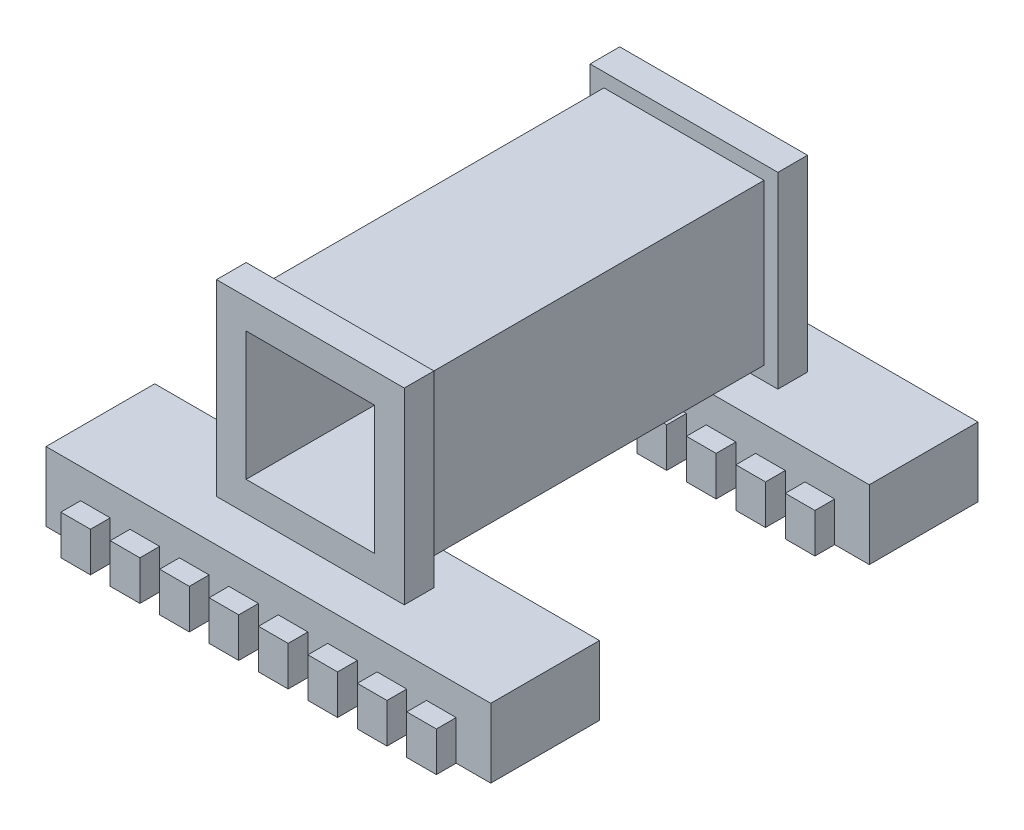
SolidWorks part; units mm, degrees
ref_plane "前视基准面" through (0, 0, 0) normal (0, 0, 1) x (1, 0, 0)
ref_plane "上视基准面" through (0, 0, 0) normal (0, 1, 0) x (1, 0, 0)
ref_plane "右视基准面" through (0, 0, 0) normal (1, 0, 0) x (0, 0, -1)
sketch "草图1" plane through (0, 0, 0) normal (0, 0, 1) x (1, 0, 0)
  line L0 (9.5, 9.5) -> (-9.5, 9.5)
  line L1 (6.5, 6.5) -> (-6.5, 6.5)
  line L2 (6.5, 6.5) -> (6.5, -6.5)
  line L3 (6.5, -6.5) -> (-6.5, -6.5)
  line L4 (-6.5, 6.5) -> (-6.5, -6.5)
  line L5 (6.5, 6.5) -> (-6.5, -6.5) construction
  line L6 (6.5, -6.5) -> (-6.5, 6.5) construction
  line L7 (-9.5, 9.5) -> (-9.5, -9.5)
  line L8 (9.5, -9.5) -> (-9.5, -9.5)
  line L9 (9.5, 9.5) -> (9.5, -9.5)
  line L10 (8.1, 8.1) -> (-8.1, 8.1)
  line L11 (-8.1, 8.1) -> (-8.1, -8.1)
  line L12 (8.1, -8.1) -> (-8.1, -8.1)
  line L13 (8.1, 8.1) -> (8.1, -8.1)
  point P0 (0, 0)
  dimension "D1" = 3
  dimension "D2" = 1.6
extrude "凸台-拉伸2" add sketch "草图1" along normal mid plane 40.8 contours L1 L4 L3 L2 | L7 L8 L9 L0 region at (0, 0, 0)
extrude "切除-拉伸1" cut sketch "草图1<3>" against normal mid plane 34.8 contours L7 L8 L9 L0 | L11 L12 L13 L10
sketch "草图1<3>" plane through (0, 0, 0) normal (0, 0, 1) x (1, 0, 0) same geometry as "草图1"
sketch "草图2" plane through (0, 0, 0) normal (0, 0, 1) x (1, 0, 0)
  line L0 (0, 0) -> (0, -9.5)
  line L1 (9.5, -9.5) -> (-9.5, -9.5) construction
  line L2 (0, -9.5) -> (-22.5, -9.5)
  line L3 (-22.5, -9.5) -> (-22.5, -16.5)
  line L4 (0, -9.5) -> (22.5, -9.5)
  line L5 (-22.5, -16.5) -> (22.5, -16.5)
  line L6 (22.5, -16.5) -> (22.5, -9.5)
extrude "凸台-拉伸4" add sketch "草图2" along normal mid plane 53.3 contours L5 L6 L4 L2 L3 region at (0, -13, 0)
extrude "切除-拉伸4" cut sketch "草图2<6>" against normal mid plane 23.3 contours L5 L6 L4 L2 L3 region at (0, -13, 0)
sketch "草图2<6>" plane through (0, 0, 0) normal (0, 0, 1) x (1, 0, 0) same geometry as "草图2"
sketch "草图4" plane through (0, 0, -26.65) normal (0, 0, -1) x (-1, 0, 0)
  line L0 (-6, -16.5) -> (-9, -16.5)
  line L1 (22.5, -16.5) -> (-22.5, -16.5) construction
  line L2 (-17.5, -16.5) -> (-17.5, -12.5)
  line L3 (-16, -16.5) -> (-19, -16.5)
  line L4 (-12.5, -12.5) -> (-12.5, -16.5)
  line L5 (-16, -16.5) -> (-16, -12.5)
  line L6 (-7.5, -16.5) -> (-7.5, -12.5)
  line L8 (-2.5, -12.5) -> (-2.5, -16.5)
  line L9 (16, -12.5) -> (19, -12.5)
  line L10 (2.5, -16.5) -> (2.5, -12.5)
  line L11 (19, -16.5) -> (19, -12.5)
  line L12 (7.5, -12.5) -> (7.5, -16.5)
  line L14 (12.5, -16.5) -> (12.5, -12.5)
  line L16 (17.5, -12.5) -> (17.5, -16.5)
  line L18 (-16, -12.5) -> (-19, -12.5)
  line L19 (-19, -16.5) -> (-19, -12.5)
  line L20 (-16, -16.5) -> (-19, -12.5) construction
  line L21 (-16, -12.5) -> (-19, -16.5) construction
  line L22 (16, -16.5) -> (19, -16.5)
  line L23 (-11, -16.5) -> (-11, -12.5)
  line L24 (-14, -16.5) -> (-11, -16.5)
  line L25 (-14, -16.5) -> (-14, -12.5)
  line L26 (-14, -12.5) -> (-11, -12.5)
  line L27 (16, -16.5) -> (16, -12.5)
  line L28 (-4, -16.5) -> (-1, -16.5)
  line L29 (-1, -16.5) -> (-1, -12.5)
  line L30 (-4, -12.5) -> (-1, -12.5)
  line L31 (-6, -16.5) -> (-6, -12.5)
  line L32 (-4, -16.5) -> (-4, -12.5)
  line L33 (-9, -16.5) -> (-9, -12.5)
  line L34 (-6, -12.5) -> (-9, -12.5)
  line L35 (14, -16.5) -> (11, -16.5)
  line L36 (14, -16.5) -> (14, -12.5)
  line L37 (14, -12.5) -> (11, -12.5)
  line L38 (11, -16.5) -> (11, -12.5)
  line L39 (6, -16.5) -> (6, -12.5)
  line L40 (6, -12.5) -> (9, -12.5)
  line L41 (9, -16.5) -> (9, -12.5)
  line L42 (6, -16.5) -> (9, -16.5)
  line L43 (4, -16.5) -> (4, -12.5)
  line L44 (4, -16.5) -> (1, -16.5)
  line L45 (1, -16.5) -> (1, -12.5)
  line L46 (4, -12.5) -> (1, -12.5)
  line L47 (-22.5, -16.5) -> (22.5, -16.5)
  line L48 (22.5, -16.5) -> (22.5, -9.5)
  line L49 (22.5, -9.5) -> (-22.5, -9.5)
  line L50 (-22.5, -9.5) -> (-22.5, -16.5)
  line L51 (-22.5, -16.5) -> (22.5, -16.5)
  line L52 (22.5, -16.5) -> (22.5, -9.5)
  line L53 (22.5, -9.5) -> (-22.5, -9.5)
  line L54 (-22.5, -9.5) -> (-22.5, -16.5)
  point P0 (-17.5, -14.5)
  line M47 (-22.5, -16.5) -> (22.5, -16.5)
  line M48 (22.5, -16.5) -> (22.5, -9.5)
  line M49 (22.5, -9.5) -> (-22.5, -9.5)
  line M50 (-22.5, -9.5) -> (-22.5, -16.5)
  dimension "D1" = 0
extrude "切除-拉伸9" cut sketch "草图4" against normal blind 2 contours L46 L43 L39 L40 L41 L38 L37 L36 L27 L9 L11 L19 L18 L5 L25 L26 L23 L33 L34 L31 L32 L30 L29 L45 M47 M48 M49 M50 region at (0, -12.3425, -26.65)
sketch "草图9" plane through (0, 0, -11.65) normal (0, 0, 1) x (1, 0, 0)
  line L36 (-4, -12.5) -> (-1, -12.5)
  line L37 (-4, -16.5) -> (-4, -12.5)
  line L38 (-6, -16.5) -> (-4, -16.5)
  line L39 (-6, -12.5) -> (-6, -16.5)
  line L40 (-9, -12.5) -> (-6, -12.5)
  line L41 (-9, -16.5) -> (-9, -12.5)
  line L42 (-11, -16.5) -> (-9, -16.5)
  line L43 (-11, -12.5) -> (-11, -16.5)
  line L44 (-14, -12.5) -> (-11, -12.5)
  line L45 (-14, -16.5) -> (-14, -12.5)
  line L46 (-16, -16.5) -> (-14, -16.5)
  line L47 (-16, -12.5) -> (-16, -16.5)
  line L48 (-19, -12.5) -> (-16, -12.5)
  line L49 (-19, -16.5) -> (-19, -12.5)
  line L50 (-22.5, -16.5) -> (-19, -16.5)
  line L51 (-22.5, -9.5) -> (-22.5, -16.5)
  line L52 (22.5, -9.5) -> (-22.5, -9.5)
  line L53 (22.5, -16.5) -> (22.5, -9.5)
  line L54 (19, -16.5) -> (22.5, -16.5)
  line L55 (19, -12.5) -> (19, -16.5)
  line L56 (16, -12.5) -> (19, -12.5)
  line L57 (16, -16.5) -> (16, -12.5)
  line L58 (14, -16.5) -> (16, -16.5)
  line L59 (14, -12.5) -> (14, -16.5)
  line L60 (11, -12.5) -> (14, -12.5)
  line L61 (11, -16.5) -> (11, -12.5)
  line L62 (9, -16.5) -> (11, -16.5)
  line L63 (9, -12.5) -> (9, -16.5)
  line L64 (6, -12.5) -> (9, -12.5)
  line L65 (6, -16.5) -> (6, -12.5)
  line L66 (4, -16.5) -> (6, -16.5)
  line L67 (4, -12.5) -> (4, -16.5)
  line L68 (1, -12.5) -> (4, -12.5)
  line L69 (1, -16.5) -> (1, -12.5)
  line L70 (-1, -16.5) -> (1, -16.5)
  line L71 (-1, -12.5) -> (-1, -16.5)
  line L72 (-4, -12.5) -> (-1, -12.5)
  line L73 (-4, -16.5) -> (-4, -12.5)
  line L74 (-6, -16.5) -> (-4, -16.5)
  line L75 (-6, -12.5) -> (-6, -16.5)
  line L76 (-9, -12.5) -> (-6, -12.5)
  line L77 (-9, -16.5) -> (-9, -12.5)
  line L78 (-11, -16.5) -> (-9, -16.5)
  line L79 (-11, -12.5) -> (-11, -16.5)
  line L80 (-14, -12.5) -> (-11, -12.5)
  line L81 (-14, -16.5) -> (-14, -12.5)
  line L82 (-16, -16.5) -> (-14, -16.5)
  line L83 (-16, -12.5) -> (-16, -16.5)
  line L84 (-19, -12.5) -> (-16, -12.5)
  line L85 (-19, -16.5) -> (-19, -12.5)
  line L86 (-22.5, -16.5) -> (-19, -16.5)
  line L87 (-22.5, -9.5) -> (-22.5, -16.5)
  line L88 (22.5, -9.5) -> (-22.5, -9.5)
  line L89 (22.5, -16.5) -> (22.5, -9.5)
  line L90 (19, -16.5) -> (22.5, -16.5)
  line L91 (19, -12.5) -> (19, -16.5)
  line L92 (16, -12.5) -> (19, -12.5)
  line L93 (16, -16.5) -> (16, -12.5)
  line L94 (14, -16.5) -> (16, -16.5)
  line L95 (14, -12.5) -> (14, -16.5)
  line L96 (11, -12.5) -> (14, -12.5)
  line L97 (11, -16.5) -> (11, -12.5)
  line L98 (9, -16.5) -> (11, -16.5)
  line L99 (9, -12.5) -> (9, -16.5)
  line L100 (6, -12.5) -> (9, -12.5)
  line L101 (6, -16.5) -> (6, -12.5)
  line L102 (4, -16.5) -> (6, -16.5)
  line L103 (4, -12.5) -> (4, -16.5)
  line L104 (1, -12.5) -> (4, -12.5)
  line L105 (1, -16.5) -> (1, -12.5)
  line L106 (-1, -16.5) -> (1, -16.5)
  line L107 (-1, -12.5) -> (-1, -16.5)
  dimension "D1" = 0
extrude "切除-拉伸10" cut sketch "草图9" against normal blind 2
sketch "草图10" plane through (0, 0, 11.65) normal (0, 0, -1) x (-1, 0, 0)
  line L36 (1, -16.5) -> (1, -12.5)
  line L37 (-1, -16.5) -> (1, -16.5)
  line L38 (-1, -12.5) -> (-1, -16.5)
  line L39 (-4, -12.5) -> (-1, -12.5)
  line L40 (-4, -16.5) -> (-4, -12.5)
  line L41 (-6, -16.5) -> (-4, -16.5)
  line L42 (-6, -12.5) -> (-6, -16.5)
  line L43 (-9, -12.5) -> (-6, -12.5)
  line L44 (-9, -16.5) -> (-9, -12.5)
  line L45 (-11, -16.5) -> (-9, -16.5)
  line L46 (-11, -12.5) -> (-11, -16.5)
  line L47 (-14, -12.5) -> (-11, -12.5)
  line L48 (-14, -16.5) -> (-14, -12.5)
  line L49 (-16, -16.5) -> (-14, -16.5)
  line L50 (-16, -12.5) -> (-16, -16.5)
  line L51 (-19, -12.5) -> (-16, -12.5)
  line L52 (-19, -16.5) -> (-19, -12.5)
  line L53 (-22.5, -16.5) -> (-19, -16.5)
  line L54 (-22.5, -9.5) -> (-22.5, -16.5)
  line L55 (22.5, -9.5) -> (-22.5, -9.5)
  line L56 (22.5, -16.5) -> (22.5, -9.5)
  line L57 (19, -16.5) -> (22.5, -16.5)
  line L58 (19, -12.5) -> (19, -16.5)
  line L59 (16, -12.5) -> (19, -12.5)
  line L60 (16, -16.5) -> (16, -12.5)
  line L61 (14, -16.5) -> (16, -16.5)
  line L62 (14, -12.5) -> (14, -16.5)
  line L63 (11, -12.5) -> (14, -12.5)
  line L64 (11, -16.5) -> (11, -12.5)
  line L65 (9, -16.5) -> (11, -16.5)
  line L66 (9, -12.5) -> (9, -16.5)
  line L67 (6, -12.5) -> (9, -12.5)
  line L68 (6, -16.5) -> (6, -12.5)
  line L69 (4, -16.5) -> (6, -16.5)
  line L70 (4, -12.5) -> (4, -16.5)
  line L71 (1, -12.5) -> (4, -12.5)
  line L72 (1, -16.5) -> (1, -12.5)
  line L73 (-1, -16.5) -> (1, -16.5)
  line L74 (-1, -12.5) -> (-1, -16.5)
  line L75 (-4, -12.5) -> (-1, -12.5)
  line L76 (-4, -16.5) -> (-4, -12.5)
  line L77 (-6, -16.5) -> (-4, -16.5)
  line L78 (-6, -12.5) -> (-6, -16.5)
  line L79 (-9, -12.5) -> (-6, -12.5)
  line L80 (-9, -16.5) -> (-9, -12.5)
  line L81 (-11, -16.5) -> (-9, -16.5)
  line L82 (-11, -12.5) -> (-11, -16.5)
  line L83 (-14, -12.5) -> (-11, -12.5)
  line L84 (-14, -16.5) -> (-14, -12.5)
  line L85 (-16, -16.5) -> (-14, -16.5)
  line L86 (-16, -12.5) -> (-16, -16.5)
  line L87 (-19, -12.5) -> (-16, -12.5)
  line L88 (-19, -16.5) -> (-19, -12.5)
  line L89 (-22.5, -16.5) -> (-19, -16.5)
  line L90 (-22.5, -9.5) -> (-22.5, -16.5)
  line L91 (22.5, -9.5) -> (-22.5, -9.5)
  line L92 (22.5, -16.5) -> (22.5, -9.5)
  line L93 (19, -16.5) -> (22.5, -16.5)
  line L94 (19, -12.5) -> (19, -16.5)
  line L95 (16, -12.5) -> (19, -12.5)
  line L96 (16, -16.5) -> (16, -12.5)
  line L97 (14, -16.5) -> (16, -16.5)
  line L98 (14, -12.5) -> (14, -16.5)
  line L99 (11, -12.5) -> (14, -12.5)
  line L100 (11, -16.5) -> (11, -12.5)
  line L101 (9, -16.5) -> (11, -16.5)
  line L102 (9, -12.5) -> (9, -16.5)
  line L103 (6, -12.5) -> (9, -12.5)
  line L104 (6, -16.5) -> (6, -12.5)
  line L105 (4, -16.5) -> (6, -16.5)
  line L106 (4, -12.5) -> (4, -16.5)
  line L107 (1, -12.5) -> (4, -12.5)
  dimension "D1" = 0
extrude "切除-拉伸11" cut sketch "草图10" against normal blind 2
sketch "草图11" plane through (0, 0, 26.65) normal (0, 0, 1) x (1, 0, 0)
  line L36 (-1, -12.5) -> (-1, -16.5)
  line L37 (-1, -16.5) -> (1, -16.5)
  line L38 (1, -16.5) -> (1, -12.5)
  line L39 (1, -12.5) -> (4, -12.5)
  line L40 (4, -12.5) -> (4, -16.5)
  line L41 (4, -16.5) -> (6, -16.5)
  line L42 (6, -16.5) -> (6, -12.5)
  line L43 (6, -12.5) -> (9, -12.5)
  line L44 (9, -12.5) -> (9, -16.5)
  line L45 (9, -16.5) -> (11, -16.5)
  line L46 (11, -16.5) -> (11, -12.5)
  line L47 (11, -12.5) -> (14, -12.5)
  line L48 (14, -12.5) -> (14, -16.5)
  line L49 (14, -16.5) -> (16, -16.5)
  line L50 (16, -16.5) -> (16, -12.5)
  line L51 (16, -12.5) -> (19, -12.5)
  line L52 (19, -12.5) -> (19, -16.5)
  line L53 (19, -16.5) -> (22.5, -16.5)
  line L54 (22.5, -16.5) -> (22.5, -9.5)
  line L55 (22.5, -9.5) -> (-22.5, -9.5)
  line L56 (-22.5, -9.5) -> (-22.5, -16.5)
  line L57 (-22.5, -16.5) -> (-19, -16.5)
  line L58 (-19, -16.5) -> (-19, -12.5)
  line L59 (-19, -12.5) -> (-16, -12.5)
  line L60 (-16, -12.5) -> (-16, -16.5)
  line L61 (-16, -16.5) -> (-14, -16.5)
  line L62 (-14, -16.5) -> (-14, -12.5)
  line L63 (-14, -12.5) -> (-11, -12.5)
  line L64 (-11, -12.5) -> (-11, -16.5)
  line L65 (-11, -16.5) -> (-9, -16.5)
  line L66 (-9, -16.5) -> (-9, -12.5)
  line L67 (-9, -12.5) -> (-6, -12.5)
  line L68 (-6, -12.5) -> (-6, -16.5)
  line L69 (-6, -16.5) -> (-4, -16.5)
  line L70 (-4, -16.5) -> (-4, -12.5)
  line L71 (-4, -12.5) -> (-1, -12.5)
  line L72 (-1, -12.5) -> (-1, -16.5)
  line L73 (-1, -16.5) -> (1, -16.5)
  line L74 (1, -16.5) -> (1, -12.5)
  line L75 (1, -12.5) -> (4, -12.5)
  line L76 (4, -12.5) -> (4, -16.5)
  line L77 (4, -16.5) -> (6, -16.5)
  line L78 (6, -16.5) -> (6, -12.5)
  line L79 (6, -12.5) -> (9, -12.5)
  line L80 (9, -12.5) -> (9, -16.5)
  line L81 (9, -16.5) -> (11, -16.5)
  line L82 (11, -16.5) -> (11, -12.5)
  line L83 (11, -12.5) -> (14, -12.5)
  line L84 (14, -12.5) -> (14, -16.5)
  line L85 (14, -16.5) -> (16, -16.5)
  line L86 (16, -16.5) -> (16, -12.5)
  line L87 (16, -12.5) -> (19, -12.5)
  line L88 (19, -12.5) -> (19, -16.5)
  line L89 (19, -16.5) -> (22.5, -16.5)
  line L90 (22.5, -16.5) -> (22.5, -9.5)
  line L91 (22.5, -9.5) -> (-22.5, -9.5)
  line L92 (-22.5, -9.5) -> (-22.5, -16.5)
  line L93 (-22.5, -16.5) -> (-19, -16.5)
  line L94 (-19, -16.5) -> (-19, -12.5)
  line L95 (-19, -12.5) -> (-16, -12.5)
  line L96 (-16, -12.5) -> (-16, -16.5)
  line L97 (-16, -16.5) -> (-14, -16.5)
  line L98 (-14, -16.5) -> (-14, -12.5)
  line L99 (-14, -12.5) -> (-11, -12.5)
  line L100 (-11, -12.5) -> (-11, -16.5)
  line L101 (-11, -16.5) -> (-9, -16.5)
  line L102 (-9, -16.5) -> (-9, -12.5)
  line L103 (-9, -12.5) -> (-6, -12.5)
  line L104 (-6, -12.5) -> (-6, -16.5)
  line L105 (-6, -16.5) -> (-4, -16.5)
  line L106 (-4, -16.5) -> (-4, -12.5)
  line L107 (-4, -12.5) -> (-1, -12.5)
  dimension "D1" = 0
extrude "切除-拉伸12" cut sketch "草图11" against normal blind 2
sketch "草图12" plane through (0, -16.5, 0) normal (0, -1, 0) x (1, 0, 0)
  line L0 (22.5, -24.65) -> (22.5, -23.4)
  line L1 (22.5, -13.65) -> (22.5, -24.65) construction
  line L2 (-19.5, 23.4) -> (19.5, 23.4)
  line L3 (19.5, -23.4) -> (19.5, -19.9)
  line L4 (19.5, -19.9) -> (-19.5, -19.9)
  line L5 (-19.5, -19.9) -> (-19.5, -23.4)
  line L6 (-19.5, -23.4) -> (19.5, -23.4)
  line L8 (-19.5, -14.9) -> (19.5, -14.9)
  line L9 (-19.5, -18.4) -> (-19.5, -14.9)
  line L10 (19.5, -18.4) -> (-19.5, -18.4)
  line L11 (19.5, -14.9) -> (19.5, -18.4)
  line L13 (-19.5, 19.9) -> (-19.5, 23.4)
  line L17 (19.5, 19.9) -> (-19.5, 19.9)
  line L18 (19.5, 23.4) -> (19.5, 19.9)
  line L19 (-19.5, 18.4) -> (-19.5, 14.9)
  line L20 (19.5, 18.4) -> (-19.5, 18.4)
  line L21 (19.5, 14.9) -> (19.5, 18.4)
  line L22 (-19.5, 14.9) -> (19.5, 14.9)
extrude "切除-拉伸13" cut sketch "草图12" against normal blind 4 contours L5 L6 L3 L4 | L19 L22 L21 L20 | L10 L9 L8 L11 | L17 L13 L2 L18 region at (0, -16.5, -21.65) region at (0, -16.5, 16.65)
